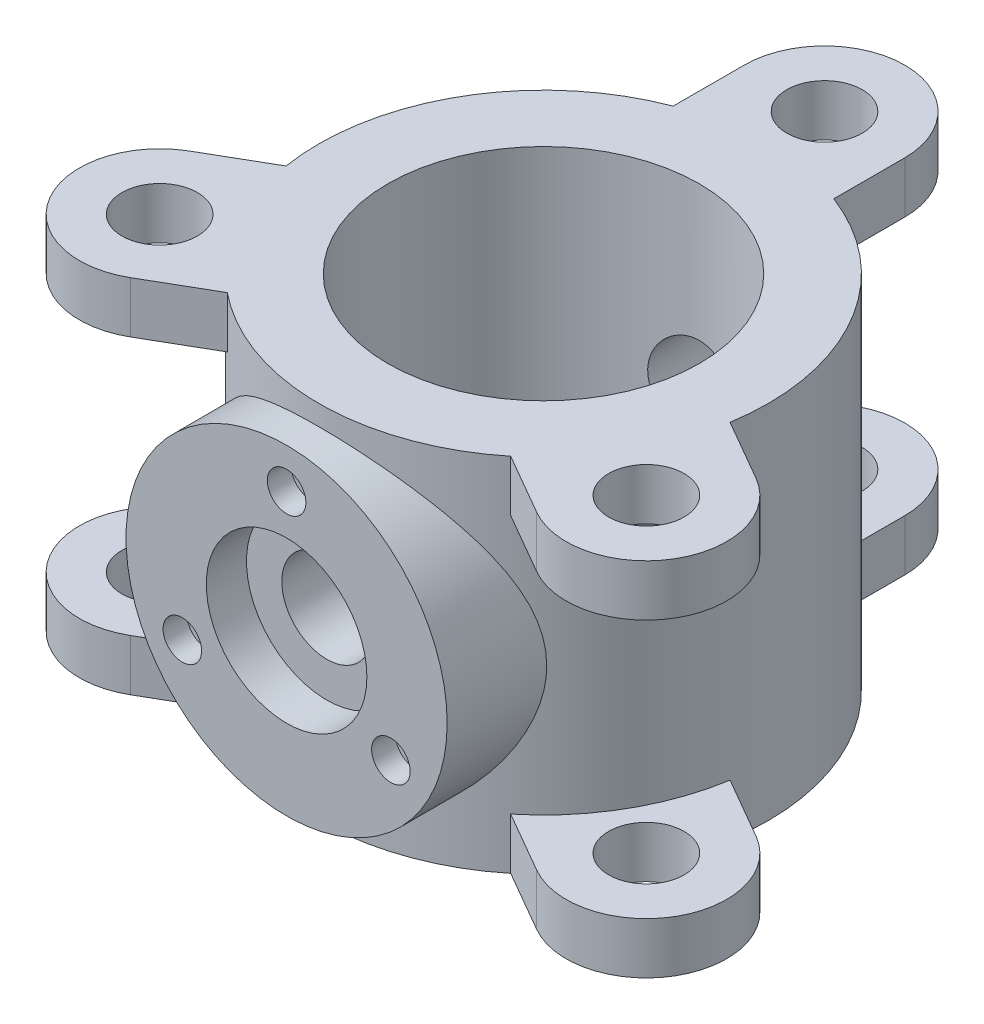
SolidWorks part; units mm, degrees
ref_plane "Front Plane" through (0, 0, 0) normal (0, 0, 1) x (1, 0, 0)
ref_plane "Top Plane" through (0, 0, 0) normal (0, 1, 0) x (1, 0, 0)
ref_plane "Right Plane" through (0, 0, 0) normal (1, 0, 0) x (0, 0, -1)
sketch "Sketch1" plane through (0, 0, 0) normal (0, 1, 0) x (1, 0, 0)
  line L0 (0, 0) -> (0, 648.2406) construction
  line L1 (-127, 444.5) -> (-127, 332.1481)
  line L2 (127, 444.5) -> (127, 332.1481)
  line L3 (448.4483, -112.2648) -> (351.1487, -56.0888)
  line L4 (321.4483, -332.2352) -> (224.1487, -276.0593)
  line L5 (-321.4483, -332.2352) -> (-224.1487, -276.0593)
  line L6 (-448.4483, -112.2648) -> (-351.1487, -56.0888)
  circle A0 centre (0, 0) radius 246.38
  circle A2 centre (0, 444.5) radius 59.69
  arc A4 (-127, 444.5) -> (127, 444.5) centre (0, 444.5) cw
  arc A5 (-127, 332.1481) -> (-351.1487, -56.0888) centre (0, 0) ccw
  arc A6 (351.1487, -56.0888) -> (127, 332.1481) centre (0, 0) ccw
  arc A7 (448.4483, -112.2648) -> (321.4483, -332.2352) centre (384.9483, -222.25) cw
  circle A8 centre (384.9483, -222.25) radius 59.69
  arc A9 (-224.1487, -276.0593) -> (224.1487, -276.0593) centre (0, 0) ccw
  arc A10 (-321.4483, -332.2352) -> (-448.4483, -112.2648) centre (-384.9483, -222.25) cw
  circle A11 centre (-384.9483, -222.25) radius 59.69
  point P31 (0, 0)
  dimension "D1" = 492.76
  dimension "D2" = 355.6
  dimension "D3" = 119.38
  dimension "D4" = 127
  dimension "D6" = 3
  dimension "D5" = 444.5
extrude "Boss-Extrude1" add sketch "Sketch1" along normal blind 81.28
sketch "Sketch2" plane through (0, 81.28, 0) normal (0, 1, 0) x (1, 0, 0)
  circle A0 centre (0, 0) radius 355.6
  circle A1 centre (0, 0) radius 246.38
extrude "Boss-Extrude2" add sketch "Sketch2" along normal blind 204.47
mirror "Mirror2" about plane through (0, 285.75, 0) normal (0, 1, 0) of bodies 102
sketch "Sketch3" plane through (0, 0, 0) normal (0, 0, 1) x (1, 0, 0)
  line L0 (0, 0) -> (0, 571.5) construction
  line L1 (224.1487, 571.5) -> (-224.1487, 571.5) construction
  circle A0 centre (0, 285.75) radius 254
  dimension "D1" = 508
extrude "Boss-Extrude3" add sketch "Sketch3" along normal blind 25.4 and the other way up to surface from offset 381 other way up to face at (0, 40.64, 0)
sketch "Sketch4" plane through (0, 0, 406.4) normal (0, 0, 1) x (1, 0, 0)
  line L0 (0, 539.75) -> (0, 31.75) construction
  circle A0 centre (0, 285.75) radius 254 construction
  circle A1 centre (0, 285.75) radius 254 construction
  circle A2 centre (0, 285.75) radius 190.5 construction
  circle A3 centre (0, 476.25) radius 30.48
  circle A4 centre (0, 285.75) radius 127
  circle A5 centre (164.9778, 190.5) radius 30.48
  circle A6 centre (-164.9778, 190.5) radius 30.48
  point P18 (0, 285.75)
  dimension "D1" = 381
  dimension "D2" = 60.96
  dimension "D3" = 254
  dimension "D4" = 3
extrude "Cut-Extrude1" cut sketch "Sketch4" against normal blind 38.1 contours A3 | A6 | A5
extrude "Cut-Extrude2" cut sketch "Sketch4<4>" against normal blind 63.5 contours A4
sketch "Sketch4<4>" plane through (0, 0, 406.4) normal (0, 0, 1) x (1, 0, 0) same geometry as "Sketch4"
sketch "Sketch5" plane through (0, 0, 342.9) normal (0, 0, 1) x (1, 0, 0)
  line L0 (0, 412.75) -> (0, 158.75) construction
  circle A0 centre (0, 285.75) radius 127 construction
  circle A1 centre (0, 285.75) radius 127 construction
  circle A2 centre (0, 285.75) radius 71.12
  dimension "D1" = 142.24
extrude "Cut-Extrude3" cut sketch "Sketch5" against normal blind 762
